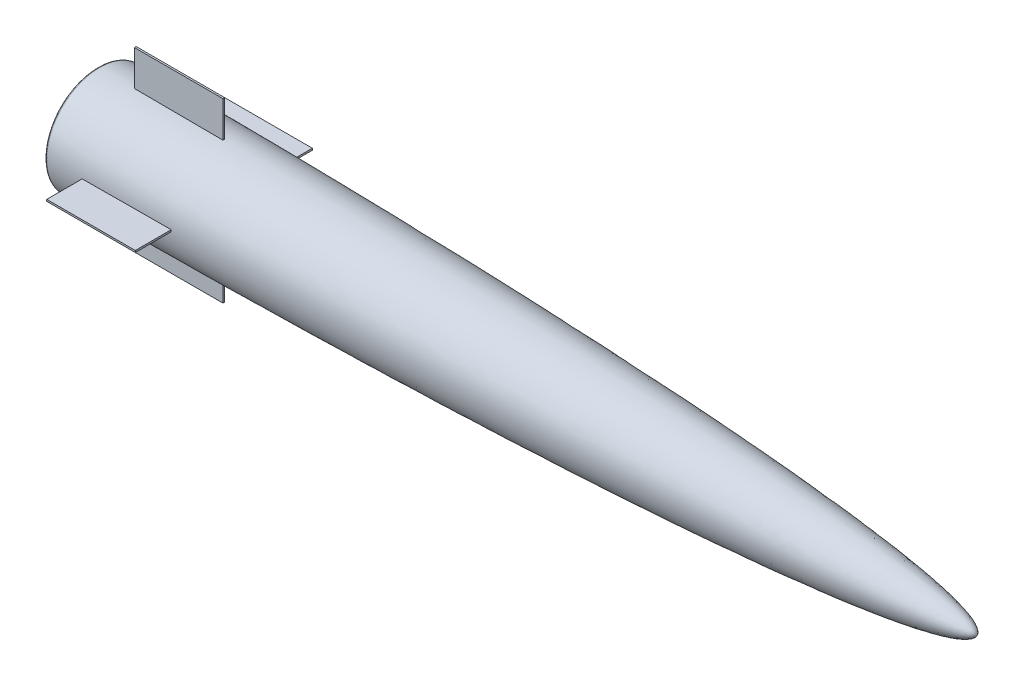
SolidWorks part; units mm, degrees
ref_plane "Front Plane" through (0, 0, 0) normal (1, 0, 0) x (0, 1, 0)
ref_plane "Top Plane" through (0, 0, 0) normal (0, 0, 1) x (0, 1, 0)
ref_plane "Right Plane" through (0, 0, 0) normal (0, 1, 0) x (-1, 0, 0)
ref_plane "Back Plane" through (-1000, 0, 0) normal (1, 0, 0) x (0, 1, 0)
sketch "body sketch" plane through (0, 0, 0) normal (0, 0, 1) x (0, 1, 0)
  line L0 (0, -55) -> (0, 55) construction
  line L1 (0, 990) -> (60, 990) construction
  line L2 (0, 990) -> (60, 990) construction
  line L3 (0, 1000) -> (0, 0)
  ellipse E0 centre (0, 990) end of major axis (0, 1980) minor radius 60 (0, 0) -> (60, 990) ccw
  ellipse E1 centre (0, 990) end of major axis (60, 990) minor radius 10 (60, 990) -> (0, 1000) ccw
  dimension "D1" = 60
  dimension "D2" = 990
  dimension "D3" = 1000
revolve "body revolve" add sketch "body sketch" angle 360 about L3
sketch "fin sketch" plane through (0, 0, 0) normal (0, 0, 1) x (0, 1, 0)
  line L0 (0, -66) -> (0, 66) construction
  line L1 (0, 950) -> (100, 950)
  line L2 (0, 950) -> (0, 850)
  line L3 (0, 850) -> (100, 850)
  line L4 (100, 950) -> (100, 850)
  point P6 (100, 915.9639)
  dimension "D1" = 850
  dimension "D2" = 100
  dimension "D3" = 100
extrude "fin extrude" add sketch "fin sketch" along normal mid plane 2
ref_axis "Rotation Axis" through (0, 0, 0) along (-1, 0, 0)
pattern_circular "fin pattern" count 4 every 90 about axis through (0, 0, 0) along (-1, 0, 0) of "fin extrude"
